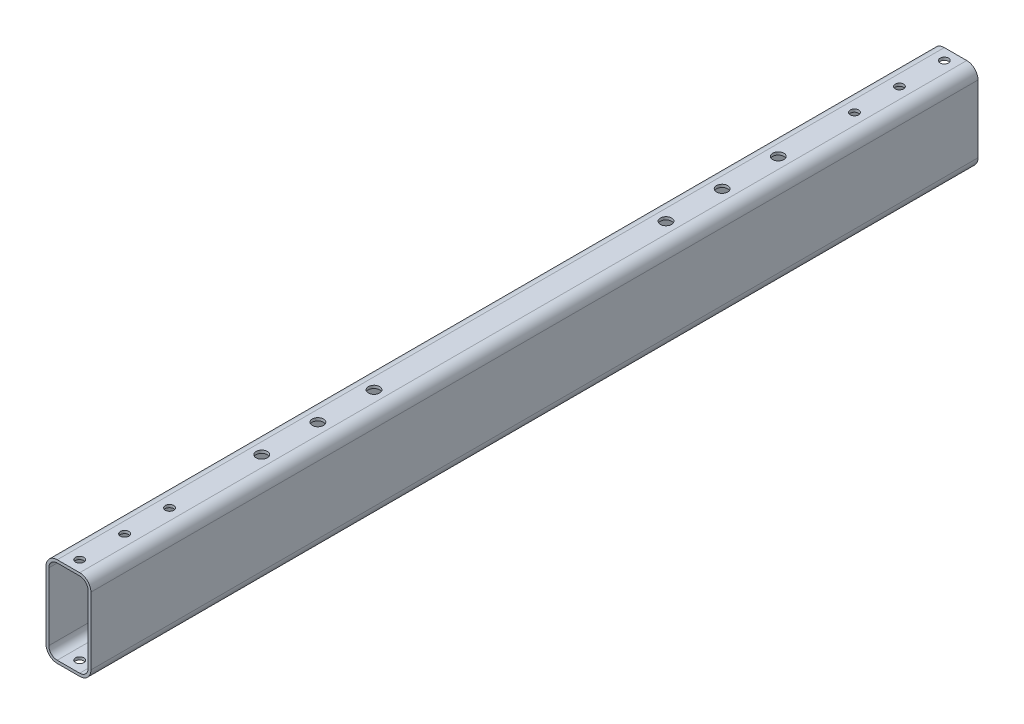
SolidWorks part; units mm, degrees
material "6061-T6 (SS)"
ref_plane "Front Plane" through (0, 0, 0) normal (0, 0, 1) x (1, 0, 0)
ref_plane "Top Plane" through (0, 0, 0) normal (0, 1, 0) x (1, 0, 0)
ref_plane "Right Plane" through (0, 0, 0) normal (1, 0, 0) x (0, 0, -1)
sketch "Sketch1" plane through (0, 0, 0) normal (0, 0, 1) x (1, 0, 0)
  line L1 (-6.35, -25.4) -> (6.35, -25.4)
  line L2 (-12.7, -19.05) -> (-12.7, 19.05)
  line L3 (-6.35, 25.4) -> (6.35, 25.4)
  line L4 (12.7, -19.05) -> (12.7, 19.05)
  line L5 (-12.7, -25.4) -> (12.7, 25.4) construction
  line L6 (-12.7, 25.4) -> (12.7, -25.4) construction
  arc A0 (-12.7, -19.05) -> (-6.35, -25.4) centre (-6.35, -19.05) ccw
  arc A1 (6.35, -25.4) -> (12.7, -19.05) centre (6.35, -19.05) ccw
  arc A2 (6.35, 25.4) -> (12.7, 19.05) centre (6.35, 19.05) cw
  arc A3 (-12.7, 19.05) -> (-6.35, 25.4) centre (-6.35, 19.05) cw
  point P0 (0, 0)
  dimension "D3" = 6.35
  dimension "D1" = 50.8
  dimension "D2" = 25.4
extrude "Extrude-Thin1" add sketch "Sketch1" along normal blind 501.65 thin thin type one direction reverse wall 1.5875
hole_wizard "3/16 (0.1875) Diameter Hole1" positions "3DSketch1" profile "Sketch3" hole size "3/16" standard "ANSI Inch" end condition through all
sketch3d "3DSketch1"
  line L1 (6.35, 25.4, 0) -> (-6.35, 25.4, 0) construction
  line L6 (0, 25.4, 501.65) -> (0, 25.4, 0) construction
  line L7 (6.35, 25.4, 501.65) -> (-6.35, 25.4, 501.65) construction
  point P57 (0, 25.4, 6.35)
  point P59 (0, 25.4, 31.75)
  point P61 (0, 25.4, 57.15)
  point P63 (0, 25.4, 469.9)
  point P65 (0, 25.4, 444.5)
  point P67 (0, 25.4, 495.3)
  dimension "D1" = 25.4
  dimension "D2" = 25.4
  dimension "D3" = 6.35
  dimension "D4" = 25.4
  dimension "D5" = 25.4
  dimension "D6" = 6.35
sketch "Sketch3" plane through (0, 25.4, 495.3) normal (1, 0, 0) x (0, 0, 1)
  line L0 (0, 0) -> (0, 50.8)
  line L1 (0, 50.8) -> (2.3812, 50.8)
  line L2 (2.3812, 50.8) -> (2.3812, 0)
  line L5 (2.3812, 0) -> (0, 0)
  line L11 (0, -6.35) -> (0, 107.95) construction
  dimension "Thru Hole Dia." = 4.7625
  dimension "Thru Hole Depth" = 50.8
hole_wizard "3/16 (0.195) Diameter Hole1" positions "Sketch4" profile "Sketch5" hole size "3/16" standard "ANSI Inch" end condition up to next
sketch "Sketch4" plane through (0, -25.4, 0) normal (0, -1, 0) x (-1, 0, 0)
  point P28 (3.175, -81.2609)
  point P31 (-3.175, -106.6609)
  point P34 (3.175, -132.0609)
  point P37 (-3.175, -157.4609)
  point P40 (3.175, -182.8609)
  point P43 (3.175, -335.2609)
  point P46 (-3.175, -360.6609)
  point P49 (3.175, -386.0609)
  point P52 (-3.175, -411.4609)
  point P60 (-3.175, -208.2609)
  point P63 (3.175, -233.6609)
  point P66 (-3.175, -259.0609)
  point P69 (3.175, -284.4609)
  point P72 (-3.175, -309.8609)
sketch "Sketch5" plane through (-3.175, -25.4, 81.2609) normal (1, 0, 0) x (0, 0, -1)
  line L0 (0, 0) -> (0, 1.5875)
  line L1 (0, 1.5875) -> (2.4765, 1.5875)
  line L2 (2.4765, 1.5875) -> (2.4765, 0)
  line L5 (2.4765, 0) -> (0, 0)
  line L11 (0, -6.35) -> (0, 107.95) construction
  dimension "Thru Hole Dia." = 4.953
  dimension "Thru Hole Depth" = 1.5875
hole_wizard "1/4 (0.25) Diameter Hole1" positions "Sketch7" profile "Sketch6" hole size "1/4" standard "ANSI Inch"
sketch "Sketch7" plane through (0, 25.4, 0) normal (0, 1, 0) x (1, 0, 0)
  point P0 (0, -100.2359)
  point P3 (0, -131.9859)
  point P6 (0, -163.7359)
  point P9 (0, -392.3608)
  point P12 (0, -360.6108)
  point P15 (0, -328.8608)
sketch "Sketch6" plane through (0, 25.4, 100.2359) normal (1, 0, 0) x (0, 0, 1)
  line L0 (0, 0) -> (0, 27.3077)
  line L1 (0, 27.3077) -> (3.175, 25.4)
  line L2 (3.175, 25.4) -> (3.175, 0)
  line L5 (3.175, 0) -> (0, 0)
  line L10 (0, 27.3077) -> (-3.175, 25.4) construction
  line L11 (0, -6.35) -> (0, 107.95) construction
  dimension "Hole Dia." = 6.35
  dimension "Hole Depth" = 25.4
  dimension "Drill Angle" = 118
